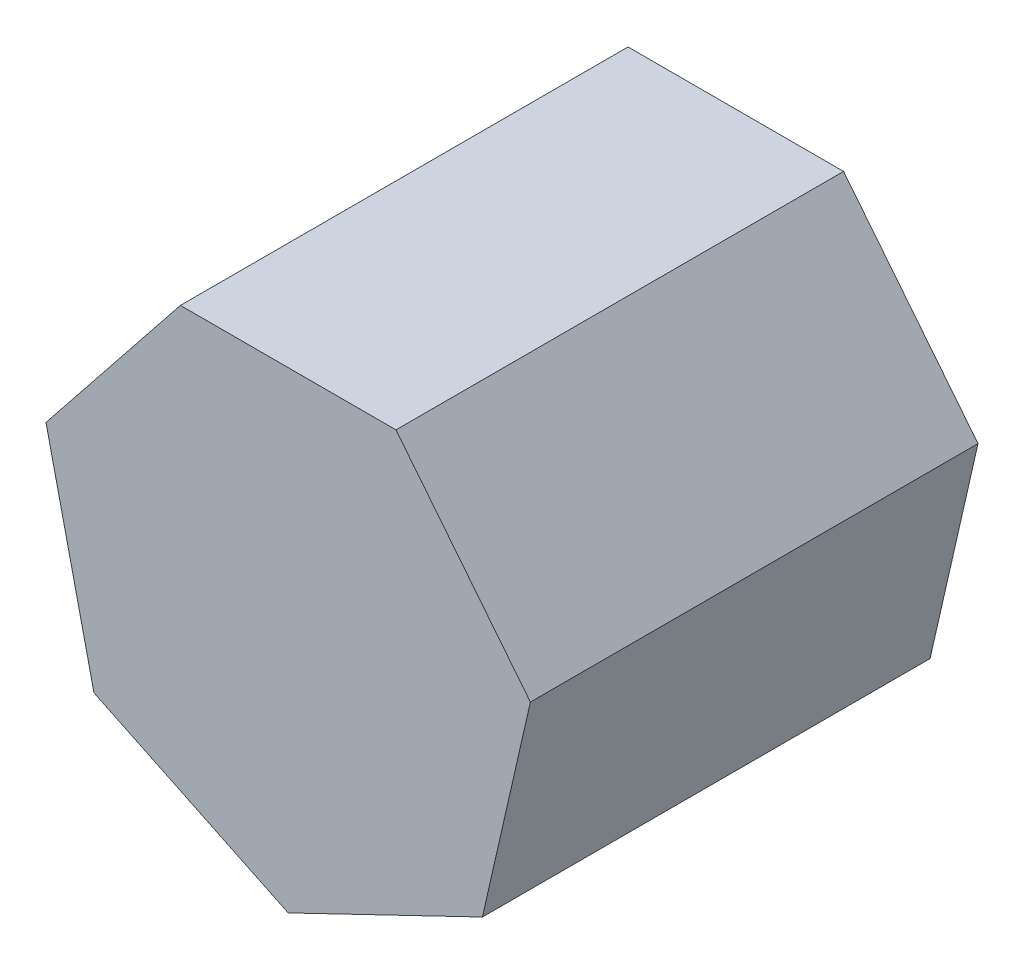
SolidWorks part; units mm, degrees
ref_plane "Front Plane" through (0, 0, 0) normal (0, 0, 1) x (1, 0, 0)
ref_plane "Top Plane" through (0, 0, 0) normal (0, 1, 0) x (1, 0, 0)
ref_plane "Right Plane" through (0, 0, 0) normal (1, 0, 0) x (0, 0, -1)
sketch "Sketch1" plane through (0, 0, 0) normal (0, 0, 1) x (1, 0, 0)
  line L1 (0, -110.9916) -> (86.7767, -69.2021)
  line L2 (86.7767, -69.2021) -> (108.2088, 24.698)
  line L3 (108.2088, 24.698) -> (48.1575, 100)
  line L4 (48.1575, 100) -> (-48.1575, 100)
  line L5 (-48.1575, 100) -> (-108.2088, 24.698)
  line L6 (-108.2088, 24.698) -> (-86.7767, -69.2021)
  line L7 (-86.7767, -69.2021) -> (0, -110.9916)
  circle A0 centre (0, 0) radius 100 construction
  dimension "D1" = 200
extrude "Boss-Extrude1" add sketch "Sketch1" along normal blind 200
sketch "Sketch2" plane through (-78.1831, 62.349, 0) normal (-0.7818, 0.6235, 0) x (0, 0, 1)
  text T0 "Andres" font "Century Gothic" height 20
extrude "Cut-Extrude1" cut sketch "Sketch2" against normal blind 1
sketch "Sketch4" plane through (-97.4928, -22.2521, 0) normal (-0.9749, -0.2225, 0) x (0, 0, 1)
  text T0 "Billy" font "Century Gothic" height 20
extrude "Cut-Extrude3" cut sketch "Sketch4" against normal blind 1
sketch "Sketch7" plane through (-43.3884, -90.0969, 0) normal (-0.4339, -0.901, 0) x (-0.901, 0.4339, 0)
  text T0 "ALEX" font "Century Gothic" height in points 72
extrude "Cut-Extrude5" cut sketch "Sketch7" against normal blind 2
